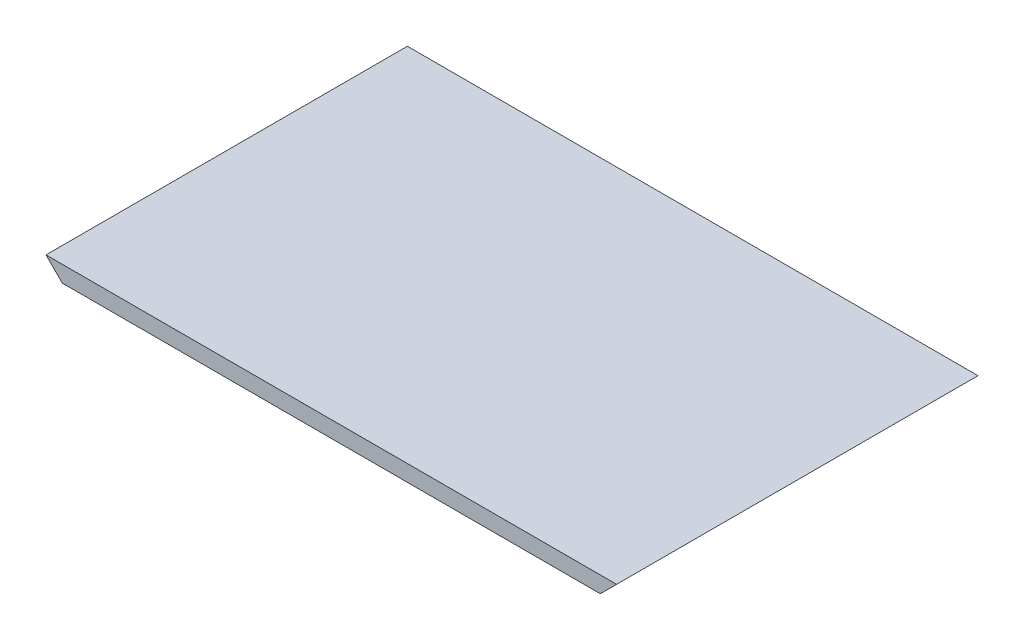
SolidWorks part; units mm, degrees
ref_plane "Front Plane" through (0, 0, 0) normal (0, 0, 1) x (1, 0, 0)
ref_plane "Top Plane" through (0, 0, 0) normal (0, 1, 0) x (1, 0, 0)
ref_plane "Right Plane" through (0, 0, 0) normal (1, 0, 0) x (0, 0, -1)
sketch "Sketch1" plane through (0, 0, 0) normal (0, 1, 0) x (1, 0, 0)
  line L0 (0, 118.0464) -> (0, -120.8757) construction
  line L1 (-169.7605, 0) -> (206.2275, 0) construction
  line L2 (-105, -66.5) -> (-105, 66.5)
  line L3 (-105, 66.5) -> (105, 66.5)
  line L4 (105, -66.5) -> (105, 66.5)
  line L5 (-105, -66.5) -> (105, -66.5)
  point P5 (0, -66.5)
  point P9 (0, 66.5)
  point P11 (105, 0)
  point P12 (-105, 0)
  dimension "D1" = 210
  dimension "D2" = 133
extrude "Boss-Extrude1" add sketch "Sketch1" along normal blind 6 contours L2 L3 L4 L5
chamfer "Chamfer1" distance 6 angle 45 2 edges at (105, 0, 0) (-105, 0, 0)
